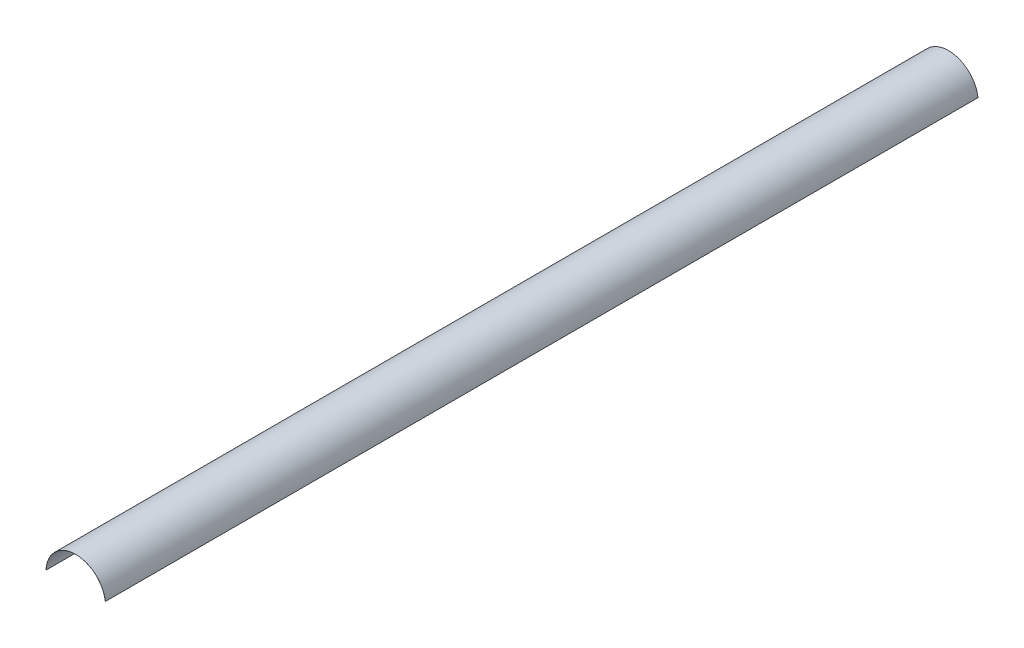
SolidWorks part; units mm, degrees
ref_plane "Front Plane" through (0, 0, 0) normal (0, 0, 1) x (1, 0, 0)
ref_plane "Top Plane" through (0, 0, 0) normal (0, 1, 0) x (1, 0, 0)
ref_plane "Right Plane" through (0, 0, 0) normal (1, 0, 0) x (0, 0, -1)
sketch "Sketch1" plane through (0, 0, 0) normal (0, 0, 1) x (1, 0, 0)
  arc A0 (0, 0) -> (207.2116, 8.6895) centre (103.9716, -4.3791) cw
extrude "Extrude-Thin1" add sketch "Sketch1" along normal blind 3048 thin thin type one direction wall 0.127
